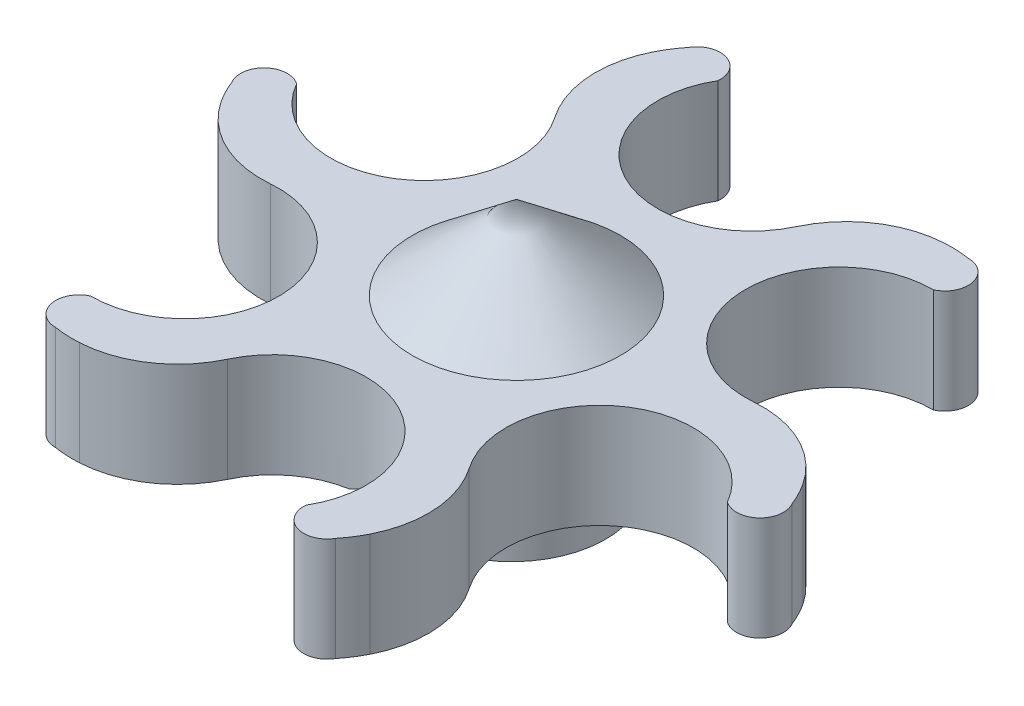
SolidWorks part; units mm, degrees
ref_plane "Front Plane" through (0, 0, 0) normal (0, 0, 1) x (1, 0, 0)
ref_plane "Top Plane" through (0, 0, 0) normal (0, 1, 0) x (1, 0, 0)
ref_plane "Right Plane" through (0, 0, 0) normal (1, 0, 0) x (0, 0, -1)
sketch "Sketch1" plane through (0, 0, 0) normal (0, 1, 0) x (1, 0, 0)
  circle A0 centre (0, 0) radius 9 construction
  arc A1 (-22.8067, 2.976) -> (-22.8067, -2.976) centre (0, 0) ccw
  arc A2 (-8.8261, 21.2391) -> (8.8261, 21.2391) centre (0, 23) ccw
  arc A3 (13.9806, 18.2632) -> (22.8067, 2.976) centre (19.9186, 11.5) ccw
  arc A4 (22.8067, -2.976) -> (13.9806, -18.2632) centre (19.9186, -11.5) ccw
  arc A5 (8.8261, -21.2391) -> (-8.8261, -21.2391) centre (0, -23) ccw
  arc A6 (-13.9806, -18.2632) -> (-22.8067, -2.976) centre (-19.9186, -11.5) ccw
  arc A7 (-22.8067, 2.976) -> (-13.9806, 18.2632) centre (-19.9186, 11.5) ccw
  arc A8 (-8.8261, 21.2391) -> (-13.9806, 18.2632) centre (0, 0) ccw
  arc A9 (13.9806, 18.2632) -> (8.8261, 21.2391) centre (0, 0) ccw
  arc A10 (22.8067, -2.976) -> (22.8067, 2.976) centre (0, 0) ccw
  arc A11 (8.8261, -21.2391) -> (13.9806, -18.2632) centre (0, 0) ccw
  arc A12 (-13.9806, -18.2632) -> (-8.8261, -21.2391) centre (0, 0) ccw
  point P18 (0, 0)
  dimension "D1" = 18
  dimension "D2" = 46
  dimension "D3" = 18
  dimension "D4" = 6
extrude "Boss-Extrude1" add sketch "Sketch1" along normal blind 10
sketch "Sketch2" plane through (0, 10, 0) normal (0, 1, 0) x (1, 0, 0)
  line L0 (0, 0) -> (-37.2267, 21.4929) construction
  line L1 (0, 0) -> (0, 42.8071) construction
  circle A0 centre (0, 23) radius 9 construction
  circle A1 centre (-19.9186, 11.5) radius 9 construction
  arc A2 (-13.9806, 18.2632) -> (-19.9806, 20.4998) centre (-19.9186, 11.5) ccw construction
  arc A3 (-19.0409, 24.7942) -> (-19.9806, 20.4998) centre (-19.0409, 22.5442) ccw construction
  arc A4 (-8.8261, 21.2391) -> (-19.0409, 24.7942) centre (-17.285, 13.3867) ccw construction
  arc A5 (-8.8261, 21.2391) -> (-13.9806, 18.2632) centre (0, 0) ccw construction
  arc A6 (-8.8261, 21.2391) -> (-13.9806, 18.2632) centre (0, 0) ccw construction
  arc A27 (8.8261, 21.2391) -> (19.0409, 24.7942) centre (17.285, 13.3867) cw
  arc A28 (19.0409, 24.7942) -> (19.9806, 20.4998) centre (19.0409, 22.5442) cw
  arc A29 (13.9806, 18.2632) -> (19.9806, 20.4998) centre (19.9186, 11.5) cw
  arc A30 (8.8261, 21.2391) -> (13.9806, 18.2632) centre (0, 0) cw
  arc A31 (22.8067, 2.976) -> (30.9928, -4.0928) centre (20.2357, -8.2759) cw
  arc A32 (30.9928, -4.0928) -> (27.7436, -7.0538) centre (29.0443, -5.2178) cw
  arc A33 (22.8067, -2.976) -> (27.7436, -7.0538) centre (19.9186, -11.5) cw
  arc A34 (22.8067, 2.976) -> (22.8067, -2.976) centre (0, 0) cw
  arc A35 (13.9806, -18.2632) -> (11.9519, -28.887) centre (2.9507, -21.6626) cw
  arc A36 (11.9519, -28.887) -> (7.763, -27.5536) centre (10.0034, -27.762) cw
  arc A37 (8.8261, -21.2391) -> (7.763, -27.5536) centre (0, -23) cw
  arc A38 (13.9806, -18.2632) -> (8.8261, -21.2391) centre (0, 0) cw
  arc A39 (-8.8261, -21.2391) -> (-19.0409, -24.7942) centre (-17.285, -13.3867) cw
  arc A40 (-19.0409, -24.7942) -> (-19.9806, -20.4998) centre (-19.0409, -22.5442) cw
  arc A41 (-13.9806, -18.2632) -> (-19.9806, -20.4998) centre (-19.9186, -11.5) cw
  arc A42 (-8.8261, -21.2391) -> (-13.9806, -18.2632) centre (0, 0) cw
  arc A43 (-22.8067, -2.976) -> (-30.9928, 4.0928) centre (-20.2357, 8.2759) cw
  arc A44 (-30.9928, 4.0928) -> (-27.7436, 7.0538) centre (-29.0443, 5.2178) cw
  arc A45 (-22.8067, 2.976) -> (-27.7436, 7.0538) centre (-19.9186, 11.5) cw
  arc A46 (-22.8067, -2.976) -> (-22.8067, 2.976) centre (0, 0) cw
  arc A47 (-13.9806, 18.2632) -> (-11.9519, 28.887) centre (-2.9507, 21.6626) cw
  arc A48 (-11.9519, 28.887) -> (-7.763, 27.5536) centre (-10.0034, 27.762) cw
  arc A49 (-8.8261, 21.2391) -> (-7.763, 27.5536) centre (0, 23) cw
  arc A50 (-13.9806, 18.2632) -> (-8.8261, 21.2391) centre (0, 0) cw
  point P55 (0, 0)
  point P63 (0, 0)
  dimension "D1" = 4.5
  dimension "D2" = 6
  dimension "D4" = 60
  dimension "D3" = 6
extrude "Boss-Extrude2" add sketch "Sketch2" against normal up to surface (10 mm away) up to face at (0, 0, 0)
fillet "Fillet1" radius 10 6 edges at (-22.8067, 5, 2.976) (-8.8261, 5, 21.2391) (13.9806, 5, 18.2632) (22.8067, 5, -2.976) (8.8261, 5, -21.2391) (-13.9806, 5, -18.2632)
sketch "Sketch3" plane through (0, 0, 0) normal (0, -1, 0) x (1, 0, 0)
  circle A0 centre (0, 0) radius 9 construction
  circle A1 centre (0, 0) radius 9
extrude "Boss-Extrude3" add sketch "Sketch3" along normal blind 6
sketch "Sketch5" plane through (0, 0, 0) normal (0, 0, 1) x (1, 0, 0)
  line L0 (-9, -6) -> (9, -6) construction
  circle A0 centre (0, -2.436) radius 1.65
  dimension "D1" = 3.3
  dimension "D2" = 3.564
extrude "Cut-Extrude1" cut sketch "Sketch5" against normal through all and the other way through all
sketch "Sketch6" plane through (0, 0, 0) normal (0, 0, 1) x (1, 0, 0)
  line L0 (0.4265, 10) -> (0.4265, 18)
  line L1 (9, 10) -> (-8.147, 10) construction
  line L2 (0.4265, 18) -> (10.4265, 10)
  line L3 (10.4265, 10) -> (0.4265, 10)
  dimension "D1" = 10
  dimension "D2" = 8
revolve "Revolve1" add sketch "Sketch6" angle 360 about L0
ref_plane "Plane3" through (0, 0, 9) normal (0, 0, 1) x (1, 0, 0)
sketch "Sketch10" plane through (0, 0, 9) normal (0, 0, 1) x (1, 0, 0)
  circle A0 centre (0, -2.436) radius 2.85
  dimension "D1" = 5.7
extrude "Cut-Extrude4" cut sketch "Sketch10" along normal through all
mirror "Mirror1" about plane through (0, 0, 0) normal (0, 0, 1) of "Cut-Extrude4"
sketch "Sketch11" plane through (0, -6, 0) normal (0, -1, 0) x (1, 0, 0)
  line L0 (-1.8064, 2.55) -> (1.8064, 2.55)
  arc A0 (-1.8064, 2.55) -> (1.8064, 2.55) centre (0, 0) ccw
  dimension "D1" = 2.55
  dimension "D2" = 6.25
extrude "Cut-Extrude5" cut sketch "Sketch11" against normal blind 16
